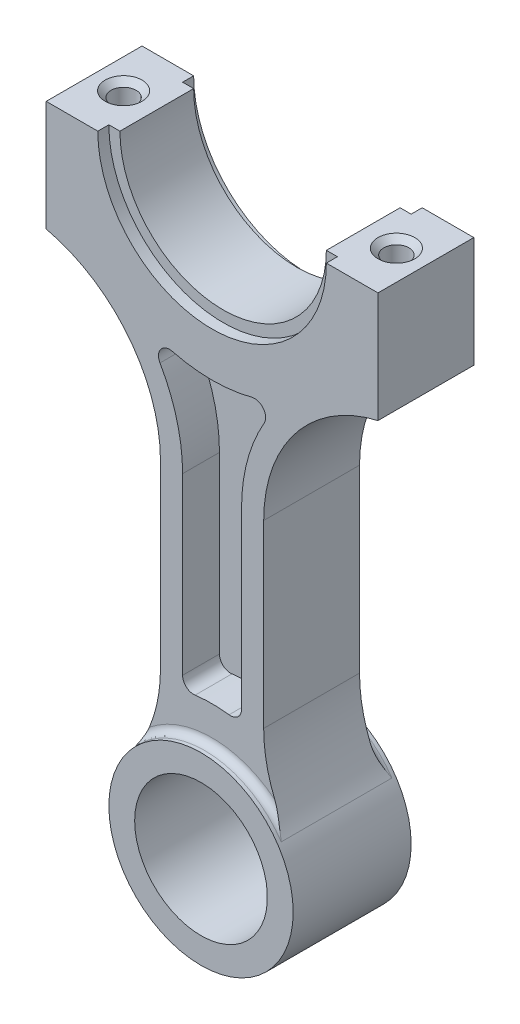
SolidWorks part; units mm, degrees
ref_plane "Спереди" through (0, 0, 0) normal (0, 0, 1) x (1, 0, 0)
ref_plane "Сверху" through (0, 0, 0) normal (0, 1, 0) x (1, 0, 0)
ref_plane "Справа" through (0, 0, 0) normal (1, 0, 0) x (0, 0, -1)
sketch "Эскиз1" plane through (0, 0, 0) normal (0, 0, 1) x (1, 0, 0)
  line L0 (-1262.1926, 0) -> (1248.5123, 0) construction
  line L1 (0, 807.1339) -> (0, -2909.8574) construction
  line L2 (-28, 0) -> (-45, 0)
  line L3 (-45, 0) -> (-45, -30)
  line L4 (-14, -68.9744) -> (-14, -117.8199)
  line L5 (14, -68.9744) -> (14, -117.8199)
  line L6 (45, 0) -> (45, -30)
  line L7 (28, 0) -> (45, 0)
  arc A0 (-45, -30) -> (-14, -68.9744) centre (-54, -68.9744) cw
  arc A1 (-14, -117.8199) -> (-20.7692, -140.0846) centre (-54, -117.8199) cw
  arc A2 (-20.7692, -140.0846) -> (20.7692, -140.0846) centre (0, -154) ccw
  arc A3 (-28, 0) -> (28, 0) centre (0, 0) ccw
  arc A4 (14, -117.8199) -> (20.7692, -140.0846) centre (54, -117.8199) ccw
  arc A5 (45, -30) -> (14, -68.9744) centre (54, -68.9744) ccw
  circle A6 centre (0, -154) radius 18
  dimension "D1" = 40
  dimension "D2" = 28
  dimension "D3" = 50
  dimension "D6" = 154
  dimension "D4" = 40
  dimension "D5" = 28
  dimension "D9" = 36
  dimension "D7" = 30
  dimension "D8" = 90
extrude "Бобышка-Вытянуть1" add sketch "Эскиз1" along normal mid plane 26
sketch "Эскиз2" plane through (0, 0, 0) normal (0, 0, 1) x (1, 0, 0)
  circle A0 centre (0, -154) radius 18
  circle A1 centre (0, -154) radius 25
  dimension "D1" = 36
extrude "Бобышка-Вытянуть2" add sketch "Эскиз2" along normal mid plane 32
fillet "Скругление4" radius 2 2 edges at (0, -129, 13) (0, -129, -13)
sketch "Эскиз8" plane through (0, 0, 13) normal (0, 0, 1) x (1, 0, 0)
  line L0 (0, 151.7865) -> (0, -342.5857) construction
  line L1 (-8, -68.9744) -> (-8, -116.3304)
  line L3 (8, -68.9744) -> (8, -116.3304)
  arc A0 (-8, -116.3304) -> (-4.6053, -119.3043) centre (-5, -116.3304) ccw
  arc A1 (-8, -68.9744) -> (-14.1322, -46.0275) centre (-54, -68.9744) ccw
  arc A2 (-14.1322, -46.0275) -> (-10.78, -41.6268) centre (-11.5321, -44.531) cw
  arc A5 (14.1322, -46.0275) -> (10.78, -41.6268) centre (11.5321, -44.531) ccw
  arc A6 (8, -68.9744) -> (14.1322, -46.0275) centre (54, -68.9744) cw
  arc A7 (8, -116.3304) -> (4.6053, -119.3043) centre (5, -116.3304) cw
  arc A8 (-10.78, -41.6268) -> (10.78, -41.6268) centre (0, 0) ccw
  arc A9 (-4.6053, -119.3043) -> (4.6053, -119.3043) centre (0, -154) cw
  point P12 (0, 0)
  point P13 (0, 0)
  point P23 (0, -342.5857)
  point P24 (0, 0)
  point P25 (0, 151.7865)
  point P29 (0, 0)
  point P30 (0, 0)
  dimension "D1" = 3
  dimension "D2" = 3
  dimension "D4" = 35
  dimension "D3" = 43
extrude "Вырез-Вытянуть16" cut sketch "Эскиз8" against normal blind 10
sketch "Эскиз4" plane through (0, 0, 13) normal (0, 0, 1) x (1, 0, 0)
  circle A0 centre (0, 0) radius 31
  dimension "D1" = 31
extrude "Вырез-Вытянуть14" cut sketch "Эскиз4" against normal blind 3
mirror "Зеркальное отражение1" about plane through (0, 0, 0) normal (0, 0, 1) of "Вырез-Вытянуть16", "Вырез-Вытянуть14"
hole_wizard "Отверстие обработанное метчиком M81" positions "Эскиз6" profile "Эскиз7" tap size "M8" standard "ISO"
sketch "Эскиз6" plane through (0, 0, 0) normal (0, 1, 0) x (1, 0, 0)
  line L0 (0, 29.9697) -> (0, -28.6074) construction
  point P0 (-37, 0)
  point P3 (37, 0)
  dimension "D1" = 74
cosmetic thread "Отверстие резьбы1" parameters "D1"=16, "D2"=8
cosmetic thread "Отверстие резьбы2" parameters "D1"=16, "D2"=8
sketch "Эскиз7" plane through (-37, 0, 0) normal (1, 0, 0) x (0, 0, 1)
  line L0 (0, 0) -> (0, 22.0429)
  line L1 (0, 22.0429) -> (3.4, 20)
  line L2 (3.4, 20) -> (3.4, 1.6)
  line L3 (3.4, 1.6) -> (5, 0)
  line L5 (5, 0) -> (0, 0)
  line L6 (-3.4, 1.6) -> (-5, 0) construction
  line L10 (0, 22.0429) -> (-3.4, 20) construction
  line L11 (0, -6.35) -> (0, 107.95) construction
  dimension "Диаметр сверла" = 6.8
  dimension "Глубина сверла" = 20
  dimension "Диаметр передней зенковки" = 10
  dimension "Угол передней зенковки" = 90
  dimension "Угол заточки сверла" = 118
